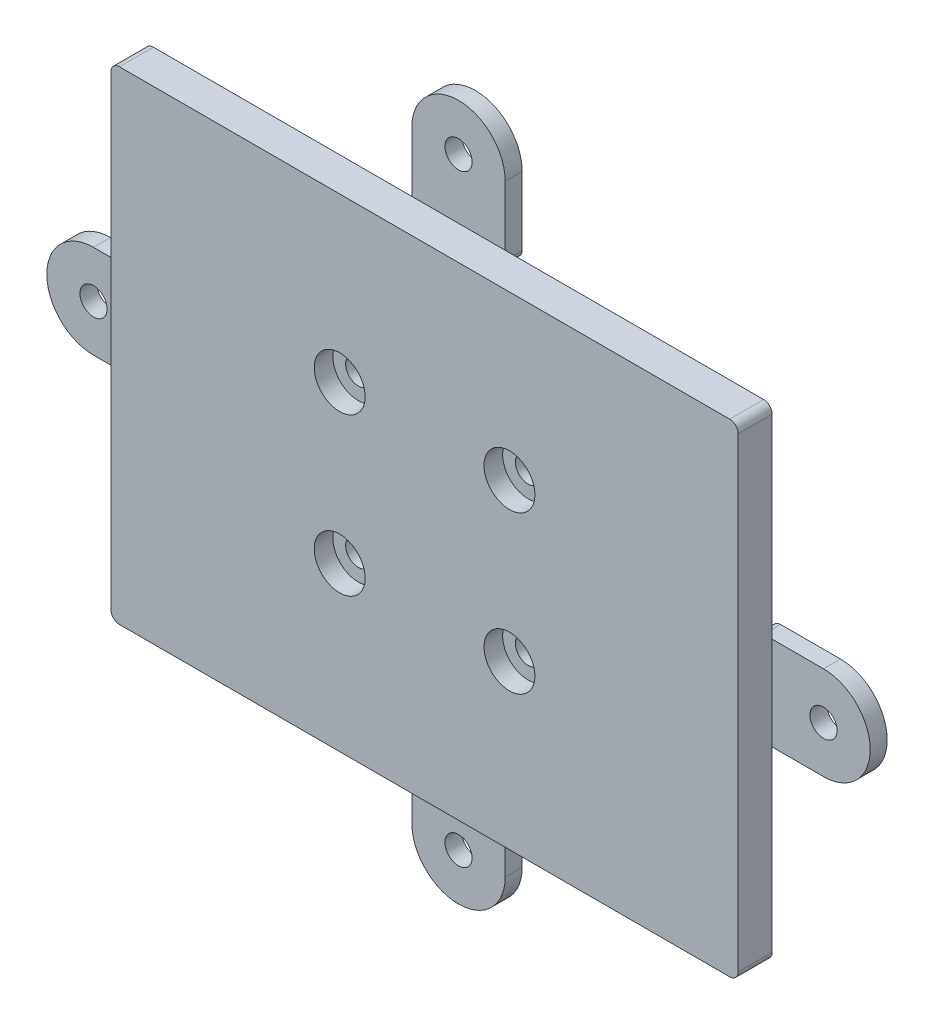
SolidWorks part; units mm, degrees
ref_plane "前视基准面" through (0, 0, 0) normal (0, 0, 1) x (1, 0, 0)
ref_plane "上视基准面" through (0, 0, 0) normal (0, 1, 0) x (1, 0, 0)
ref_plane "右视基准面" through (0, 0, 0) normal (1, 0, 0) x (0, 0, -1)
sketch "草图1" plane through (0, 0, 0) normal (0, 0, 1) x (1, 0, 0)
  line L1 (-36.95, 28.45) -> (36.95, 28.45)
  line L2 (-36.95, 28.45) -> (-36.95, -28.45)
  line L3 (-36.95, -28.45) -> (36.95, -28.45)
  line L4 (36.95, 28.45) -> (36.95, -28.45)
  line L5 (-36.95, 28.45) -> (36.95, -28.45) construction
  line L6 (-36.95, -28.45) -> (36.95, 28.45) construction
  point P0 (0, 0)
  dimension "D1" = 56.9
  dimension "D2" = 73.9
extrude "凸台-拉伸1" add sketch "草图1" along normal blind 4
sketch "草图2" plane through (0, 0, 4) normal (0, 0, 1) x (1, 0, 0)
  line L1 (-10, 9.25) -> (10, 9.25) construction
  line L2 (-10, 9.25) -> (-10, -9.25) construction
  line L3 (-10, -9.25) -> (10, -9.25) construction
  line L4 (10, 9.25) -> (10, -9.25) construction
  line L5 (-10, 9.25) -> (10, -9.25) construction
  line L6 (-10, -9.25) -> (10, 9.25) construction
  point P0 (0, 0)
  dimension "D1" = 20
  dimension "D2" = 18.5
hole_wizard "孔1" positions "3D草图1" profile "草图3" legacy
sketch3d "3D草图1"
  point P0 (-10, 9.25, 4)
  point P3 (10, 9.25, 4)
  point P6 (10, -9.25, 4)
  point P9 (-10, -9.25, 4)
sketch "草图3" plane through (-10, 9.25, 4) normal (1, 0, 0) x (0, -1, 0)
  line L0 (0, 0) -> (0, 4)
  line L1 (0, 4) -> (1.5, 4)
  line L2 (1.5, 4) -> (1.5, 2.2)
  line L3 (1.5, 2.2) -> (3, 2.2)
  line L4 (3, 2.2) -> (3, 0)
  line L5 (3, 0) -> (0, 0)
  line L6 (0, 110) -> (0, -10) construction
  dimension "直径" = 3
  dimension "深度" = 4
  dimension "柱坑直径" = 6
  dimension "柱坑深度" = 2.2
sketch "草图4" plane through (0, 0, 0) normal (0, 0, -1) x (-1, 0, 0)
  line L6 (0, 35.5) -> (0, -35.5) construction
  line L7 (3.5, 35.5) -> (3.5, -35.5)
  line L8 (-3.5, 35.5) -> (-3.5, -35.5)
  line L10 (-43, -1) -> (43, -1) construction
  line L11 (-43, 2.5) -> (43, 2.5)
  line L12 (-43, -4.5) -> (43, -4.5)
  arc A2 (3.5, 35.5) -> (-3.5, 35.5) centre (0, 35.5) ccw
  arc A3 (-3.5, -35.5) -> (3.5, -35.5) centre (0, -35.5) ccw
  arc A4 (-43, 2.5) -> (-43, -4.5) centre (-43, -1) ccw
  arc A5 (43, -4.5) -> (43, 2.5) centre (43, -1) ccw
  point P2 (0, 0)
  point P7 (0, -1)
  line M11 (-36.95, 28.45) -> (-36.95, -28.45)
  line M12 (-36.95, -28.45) -> (36.95, -28.45)
  line M13 (36.95, -28.45) -> (36.95, 28.45)
  line M14 (36.95, 28.45) -> (-36.95, 28.45)
  dimension "D2" = 7
  dimension "D1" = 71
  dimension "D3" = 86
  dimension "D4" = 1
  dimension "D5" = 7
extrude "凸台-拉伸2" add sketch "草图4" along normal blind 2 contours L7 A2 L8 M14 | L8 L11 L7 M14 | L7 L12 L11 M13 | L12 A5 L11 M13 | L8 L12 L7 L11 | L12 L8 L11 M11 | L12 L8 L7 M12 | L11 A4 L12 M11 | L8 A3 L7 M12 region at (0, 33.3806, 0) region at (0, 15.475, 0) region at (-20.225, -1, 0) region at (0, -1, 0) region at (0, -16.475, 0) region at (20.225, -1, 0) region at (-41.3841, -1, 0) region at (0, -33.3806, 0) region at (41.3841, -1, 0)
sketch "草图5" plane through (0, 0, -2) normal (0, 0, -1) x (-1, 0, 0)
  line L8 (3.5, 2.5) -> (3.5, 35.5)
  line L9 (-3.5, 35.5) -> (-3.5, 2.5)
  line L10 (-3.5, 2.5) -> (-43, 2.5)
  line L11 (-43, -4.5) -> (-3.5, -4.5)
  line L12 (-3.5, -4.5) -> (-3.5, -35.5)
  line L13 (3.5, -35.5) -> (3.5, -4.5)
  line L14 (3.5, -4.5) -> (43, -4.5)
  line L15 (43, 2.5) -> (3.5, 2.5)
  line L16 (3.5, 2.5) -> (3.5, 35.5) construction
  line L17 (-3.5, 35.5) -> (-3.5, 2.5) construction
  line L18 (-3.5, 2.5) -> (-43, 2.5) construction
  line L19 (-43, -4.5) -> (-3.5, -4.5) construction
  line L20 (-3.5, -4.5) -> (-3.5, -35.5) construction
  line L21 (3.5, -35.5) -> (3.5, -4.5) construction
  line L22 (3.5, -4.5) -> (43, -4.5) construction
  line L23 (43, 2.5) -> (3.5, 2.5) construction
  arc A4 (3.5, 35.5) -> (-3.5, 35.5) centre (0, 35.5) ccw
  arc A5 (-43, 2.5) -> (-43, -4.5) centre (-43, -1) ccw
  arc A6 (-3.5, -35.5) -> (3.5, -35.5) centre (0, -35.5) ccw
  arc A7 (43, -4.5) -> (43, 2.5) centre (43, -1) ccw
  arc A8 (3.5, 35.5) -> (-3.5, 35.5) centre (0, 35.5) ccw construction
  arc A9 (-43, 2.5) -> (-43, -4.5) centre (-43, -1) ccw construction
  arc A10 (-3.5, -35.5) -> (3.5, -35.5) centre (0, -35.5) ccw construction
  arc A11 (43, -4.5) -> (43, 2.5) centre (43, -1) ccw construction
  dimension "D1" = 0
hole_wizard "孔2" positions "3D草图2" profile "草图6" legacy end condition through all
sketch3d "3D草图2"
  point P0 (43, -1, -2)
  point P3 (0, 35.5, -2)
  point P6 (-43, -1, -2)
  point P9 (0, -35.5, -2)
sketch "草图6" plane through (43, -1, -2) normal (1, 0, 0) x (0, 1, 0)
  line L0 (0, 0) -> (0, 6)
  line L1 (0, 6) -> (1.6, 6)
  line L2 (1.6, 6) -> (1.6, 0)
  line L3 (1.6, 0) -> (0, 0)
  line L4 (0, 110) -> (0, -10) construction
  dimension "直径" = 3.2
  dimension "深度" = 6
chamfer "倒角1" distance 2 distance2 1 2 edges at (-3.5, 15.475, 0) (-20.225, 2.5, 0) first distance on face at (-3.5, 20.89, -0.8) first distance on face at (-25.99, 2.5, -0.8)
chamfer "倒角2" distance 1 distance2 2 2 edges at (-3.5, -16.475, 0) (-20.225, -4.5, 0) first distance on face at (-8.5, -9.25, 0)
chamfer "倒角3" distance 1 distance2 2 4 edges at (3.5, -16.475, 0) (20.225, -4.5, 0) (20.225, 2.5, 0) (3.5, 15.475, 0) first distance on face at (11.5, -9.25, 0) first distance on face at (11.5, 9.25, 0)
sketch "草图7" plane through (0, 0, 0) normal (0, 0, -1) x (-1, 0, 0)
  line L0 (36.95, -4.5) -> (36.95, 2.5) construction
  line L1 (36.95, 2.5) -> (43, 2.5) construction
  line L2 (43, -4.5) -> (36.95, -4.5) construction
  line L3 (-3.5, -28.45) -> (3.5, -28.45) construction
  line L4 (3.5, -28.45) -> (3.5, -35.5) construction
  line L5 (-3.5, -35.5) -> (-3.5, -28.45) construction
  line L6 (-36.95, 2.5) -> (-36.95, -4.5) construction
  line L7 (-36.95, -4.5) -> (-43, -4.5) construction
  line L8 (-43, 2.5) -> (-36.95, 2.5) construction
  line L9 (3.5, 28.45) -> (-3.5, 28.45) construction
  line L10 (-3.5, 28.45) -> (-3.5, 35.5) construction
  line L11 (3.5, 35.5) -> (3.5, 28.45) construction
  line L12 (36.95, -4.5) -> (36.95, 2.5)
  line L13 (36.95, 2.5) -> (43, 2.5)
  line L14 (43, -4.5) -> (36.95, -4.5)
  line L15 (-3.5, -28.45) -> (3.5, -28.45)
  line L16 (3.5, -28.45) -> (3.5, -35.5)
  line L17 (-3.5, -35.5) -> (-3.5, -28.45)
  line L18 (-36.95, 2.5) -> (-36.95, -4.5)
  line L19 (-36.95, -4.5) -> (-43, -4.5)
  line L20 (-43, 2.5) -> (-36.95, 2.5)
  line L21 (3.5, 28.45) -> (-3.5, 28.45)
  line L22 (-3.5, 28.45) -> (-3.5, 35.5)
  line L23 (3.5, 35.5) -> (3.5, 28.45)
  line L24 (-43, 4.5) -> (-34.95, 4.5)
  line L25 (-34.95, 4.5) -> (-34.95, -6.5)
  line L26 (-34.95, -6.5) -> (-43, -6.5)
  line L27 (-5.5, 26.45) -> (-5.5, 35.5)
  line L28 (5.5, 35.5) -> (5.5, 26.45)
  line L29 (5.5, 26.45) -> (-5.5, 26.45)
  line L30 (34.95, 4.5) -> (43, 4.5)
  line L31 (43, -6.5) -> (34.95, -6.5)
  line L32 (34.95, -6.5) -> (34.95, 4.5)
  line L33 (5.5, -26.45) -> (5.5, -35.5)
  line L34 (-5.5, -35.5) -> (-5.5, -26.45)
  line L35 (-5.5, -26.45) -> (5.5, -26.45)
  arc A0 (43, -4.5) -> (43, 2.5) centre (43, -1) ccw construction
  arc A1 (-3.5, -35.5) -> (3.5, -35.5) centre (0, -35.5) ccw construction
  arc A2 (-43, 2.5) -> (-43, -4.5) centre (-43, -1) ccw construction
  arc A3 (3.5, 35.5) -> (-3.5, 35.5) centre (0, 35.5) ccw construction
  circle A4 centre (43, -1) radius 1.6 construction
  arc A5 (43, -4.5) -> (43, 2.5) centre (43, -1) ccw
  arc A6 (-3.5, -35.5) -> (3.5, -35.5) centre (0, -35.5) ccw
  arc A7 (-43, 2.5) -> (-43, -4.5) centre (-43, -1) ccw
  arc A8 (3.5, 35.5) -> (-3.5, 35.5) centre (0, 35.5) ccw
  circle A9 centre (43, -1) radius 1.6
  circle A10 centre (0, 35.5) radius 1.6 construction
  circle A11 centre (-43, -1) radius 1.6 construction
  circle A12 centre (0, -35.5) radius 1.6 construction
  circle A13 centre (0, 35.5) radius 1.6
  circle A14 centre (-43, -1) radius 1.6
  circle A15 centre (0, -35.5) radius 1.6
  arc A16 (-43, 4.5) -> (-43, -6.5) centre (-43, -1) ccw
  arc A17 (5.5, 35.5) -> (-5.5, 35.5) centre (0, 35.5) ccw
  arc A18 (43, -6.5) -> (43, 4.5) centre (43, -1) ccw
  arc A19 (-5.5, -35.5) -> (5.5, -35.5) centre (0, -35.5) ccw
  line M18 (-36.95, 28.45) -> (-36.95, 3.5)
  line M19 (-36.95, 3.5) -> (-4.5, 3.5)
  line M20 (-4.5, 3.5) -> (-4.5, 28.45)
  line M21 (-4.5, 28.45) -> (-36.95, 28.45)
  dimension "D1" = 2
extrude "凸台-拉伸3" add sketch "草图7" along normal blind 2 contours L24 A16 L26 L25 A7 L20 L18 L19 M19 M18 | L25 L24 M18 M19 | L34 A19 L33 L35 A6 L17 L15 L16 | L31 A18 L30 L32 A5 L14 L12 L13 | L28 A17 L27 L29 A8 L23 L21 L22 M21 M20 | L29 L27 M20 M21 region at (39.975, 4.3255, 0) region at (35.95, 4, 0) region at (5, 27.45, 0) region at (5.3176, 31.975, 0) region at (-38.975, 4.3255, 0) region at (-5.3176, -30.975, 0)
fillet "圆角3" radius 1 8 edges at (-34.95, -6.5, -1) (-34.95, 4.5, -1) (5.5, -26.45, -1) (-5.5, -26.45, -1) (-5.5, 26.45, -1) (5.5, 26.45, -1) (34.95, 4.5, -1) (34.95, -6.5, -1)
fillet "圆角4" radius 1 4 edges at (-36.95, -28.45, 2) (-36.95, 28.45, 2) (36.95, 28.45, 2) (36.95, -28.45, 2)
